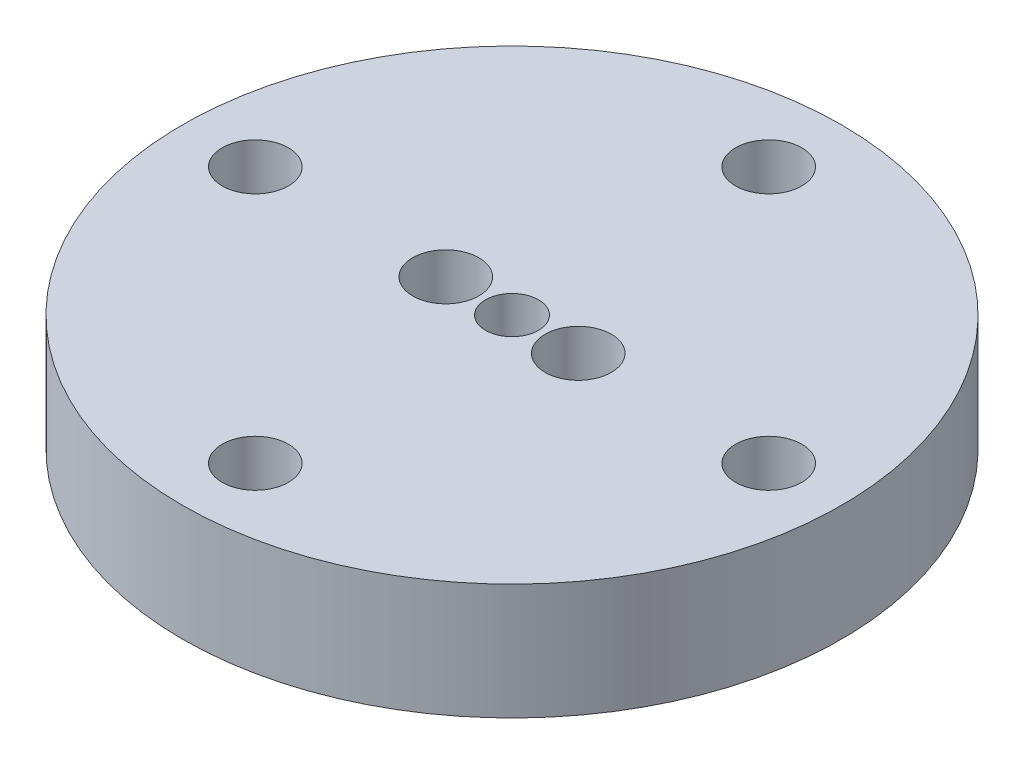
SolidWorks part; units mm, degrees
ref_plane "Front Plane" through (0, 0, 0) normal (0, 0, 1) x (1, 0, 0)
ref_plane "Top Plane" through (0, 0, 0) normal (0, 1, 0) x (1, 0, 0)
ref_plane "Right Plane" through (0, 0, 0) normal (1, 0, 0) x (0, 0, -1)
sketch "Sketch1" plane through (0, 0, 0) normal (0, 1, 0) x (1, 0, 0)
  circle A0 centre (0, 0) radius 15.5 construction
  circle A1 centre (0, 15.5) radius 2
  circle A2 centre (15.5, 0) radius 2
  circle A3 centre (0, -15.5) radius 2
  circle A4 centre (-15.5, 0) radius 2
  circle A5 centre (0, 0) radius 19.9
  circle A6 centre (0, 0) radius 4 construction
  circle A7 centre (-4, 0) radius 2
  circle A8 centre (4, 0) radius 2
  circle A9 centre (0, 0) radius 1.6
  point P14 (0, 0)
  dimension "D1" = 31
  dimension "D2" = 4
  dimension "D4" = 39.8
  dimension "D5" = 8
  dimension "D6" = 4
  dimension "D7" = 3.2
  dimension "D3" = 4
extrude "Boss-Extrude1" add sketch "Sketch1" along normal blind 7
